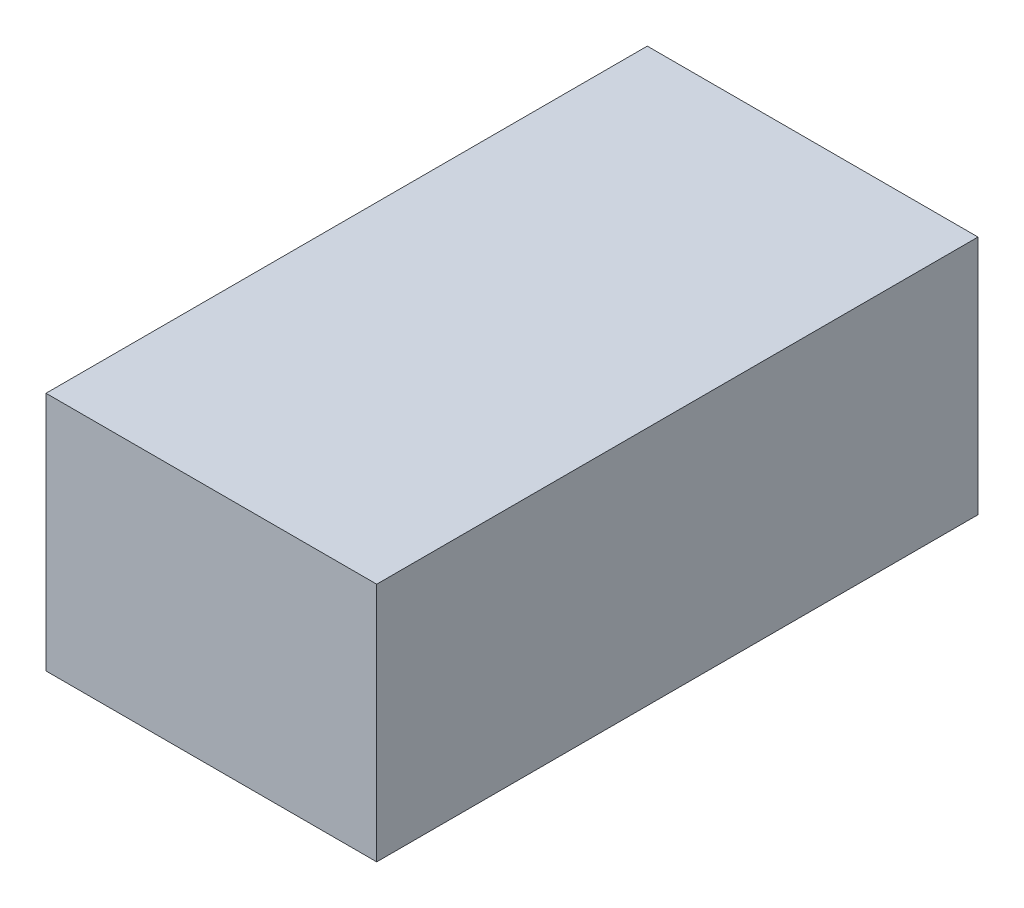
SolidWorks part; units mm, degrees
ref_plane "前视基准面" through (0, 0, 0) normal (0, 0, 1) x (1, 0, 0)
ref_plane "上视基准面" through (0, 0, 0) normal (0, 1, 0) x (1, 0, 0)
ref_plane "右视基准面" through (0, 0, 0) normal (1, 0, 0) x (0, 0, -1)
other "Configuration Table"
sketch "草图1" plane through (0, 0, 0) normal (0, 0, 1) x (1, 0, 0)
  line L1 (0, 0) -> (2, 0)
  line L2 (0, 0) -> (0, -1.5)
  line L3 (0, -1.5) -> (2, -1.5)
  line L4 (2, 0) -> (2, -1.5)
  line L5 (0, 0) -> (1.3, 0)
  line L6 (0, 0) -> (0, 5)
  line L7 (0, 5) -> (1.3, 5)
  line L8 (1.3, 0) -> (1.3, 5)
  dimension "D1" = 5
  dimension "D2" = 1.5
  dimension "D3" = 2
  dimension "D4" = 1.3
revolve "旋转1" add sketch "草图1" angle 360 about L6
sketch "草图2" plane through (0, 0, 0) normal (0, 0, 1) x (1, 0, 0)
  line L1 (0.75, 5) -> (0, 5)
  line L2 (0.75, 5) -> (0.75, 0)
  line L3 (0.75, 0) -> (0, 0)
  line L4 (0, 5) -> (0, 0)
  line L5 (0, 0) -> (2.5, 0)
  line L6 (0, 0) -> (0, -2)
  line L7 (0, -2) -> (2.5, -2)
  line L8 (2.5, 0) -> (2.5, -2)
  line L13 (-5.5, 6) -> (5.5, 6)
  line L14 (-5.5, 6) -> (-5.5, -2)
  line L15 (-5.5, -2) -> (5.5, -2)
  line L16 (5.5, 6) -> (5.5, -2)
  line L17 (0, 1) -> (1.8, 1)
  line L18 (0, 1) -> (0, 0)
  line L19 (0, 0) -> (1.8, 0)
  line L20 (1.8, 1) -> (1.8, 0)
  point P7 (0, 6)
  dimension "D1" = 3
  dimension "D2" = 0.75
  dimension "D3" = 2.5
  dimension "D4" = 1
  dimension "D5" = 1.8
  dimension "D6" = 1
  dimension "D7" = 5
  dimension "D8" = 2
extrude "凸台-拉伸1" add sketch "草图2" along normal mid plane 20 contours L13 L16 L15 L14
revolve "切除-旋转1" cut sketch "草图2<4>" angle 360 about L6
sketch "草图2<4>" plane through (0, 0, 0) normal (0, 0, 1) x (1, 0, 0) same geometry as "草图2"
revolve "旋转2" add sketch "草图1<3>" angle 360 about L6
sketch "草图1<3>" plane through (0, 0, 0) normal (0, 0, 1) x (1, 0, 0) same geometry as "草图1"
